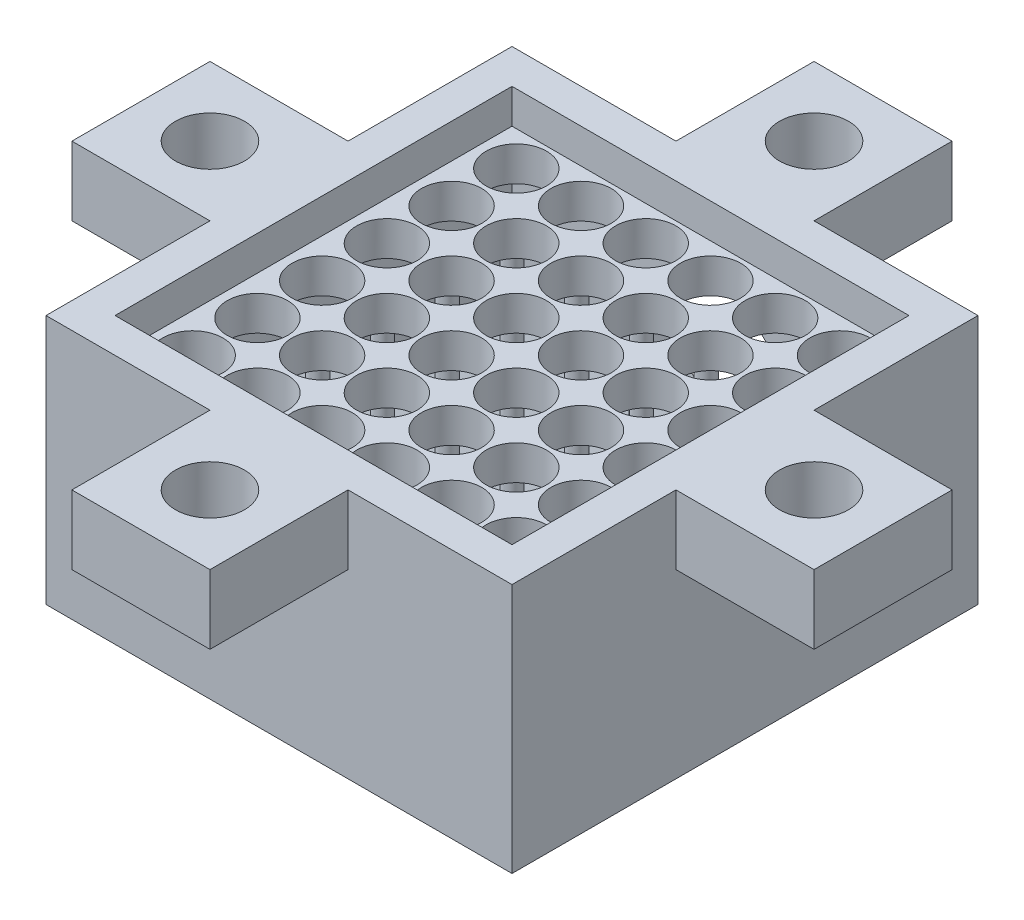
SolidWorks part; units mm, degrees
note: '?' marks a value the reader was unsure of.
ref_plane "Front Plane" through (0, 0, 0) normal (0, 0, 1) x (1, 0, 0)
ref_plane "Top Plane" through (0, 0, 0) normal (0, 1, 0) x (1, 0, 0)
ref_plane "Right Plane" through (0, 0, 0) normal (1, 0, 0) x (0, 0, -1)
sketch "Sketch1" plane through (0, 0, 0) normal (0, 1, 0) x (1, 0, 0)
  line L0 (-13.5, 13.5) -> (13.5, 13.5)
  line L1 (-11.5, -11.5) -> (11.5, -11.5)
  line L2 (-11.5, -11.5) -> (-11.5, 11.5)
  line L3 (-11.5, 11.5) -> (11.5, 11.5)
  line L4 (11.5, -11.5) -> (11.5, 11.5)
  line L5 (-11.5, -11.5) -> (11.5, 11.5) construction
  line L6 (-11.5, 11.5) -> (11.5, -11.5) construction
  line L7 (13.5, -13.5) -> (13.5, 13.5)
  line L8 (-13.5, -13.5) -> (13.5, -13.5)
  line L9 (-13.5, -13.5) -> (-13.5, 13.5)
  point P0 (0, 0)
  dimension "D1" = 23
  dimension "D2" = 2
extrude "Boss-Extrude1" add sketch "Sketch1" along normal blind 2
sketch "Sketch2" plane through (0, 0, 0) normal (0, -1, 0) x (1, 0, 0)
  line L1 (-13.5, 13.5) -> (13.5, 13.5)
  line L2 (-13.5, 13.5) -> (-13.5, -13.5)
  line L3 (-13.5, -13.5) -> (13.5, -13.5)
  line L4 (13.5, 13.5) -> (13.5, -13.5)
  line L5 (-13.5, 13.5) -> (13.5, -13.5) construction
  line L6 (-13.5, -13.5) -> (13.5, 13.5) construction
  point P0 (0, 0)
extrude "Boss-Extrude2" add sketch "Sketch2" along normal blind 2
sketch "Sketch12" plane through (-13.5, 0, 0) normal (-1, 0, 0) x (0, 0, 1)
  line L0 (-13.5, 2) -> (13.5, 2) construction
  line L1 (-4, -2) -> (4, -2)
  line L2 (-4, -2) -> (-4, 2)
  line L3 (-4, 2) -> (4, 2)
  line L4 (4, -2) -> (4, 2)
  line L5 (-4, -2) -> (4, 2) construction
  line L6 (-4, 2) -> (4, -2) construction
  point P0 (0, 0)
  dimension "D1" = 8
extrude "Boss-Extrude9" add sketch "Sketch12" along normal blind 8
ref_axis "Axis2" through (0, 0, 0) along (0, -1, 0)?
pattern_circular "CirPattern1" count 4 over 360 about axis through (0, 0, 0) along (0, 1, 0) of "Boss-Extrude9"
sketch "Sketch20" plane through (0, 2, 0) normal (0, 1, 0) x (1, 0, 0)
  line L0 (4, -13.5) -> (-4, -21.5) construction
  circle A0 centre (0, -17.5) radius 2
  dimension "D1" = 4
extrude "Cut-Extrude11" cut sketch "Sketch20" against normal up to next
pattern_circular "CirPattern2" count 4 over 360 about axis through (0, 0, 0) along (0, 1, 0) of "Cut-Extrude11"
ref_plane "Plane1" through (0, 0, 0) normal (1, 0, 0) x (0, 0, -1)
sketch "Sketch13" plane through (0, 0, 0) normal (0, 1, 0) x (1, 0, 0)
  line L0 (11.5, -11.5) -> (11.5, 11.5) construction
  line L1 (11.5, 11.5) -> (-11.5, 11.5) construction
  circle A0 centre (9.5, 9.5) radius 1.75
  dimension "D1" = 3.5
  dimension "D2" = 2
  dimension "D3" = 2
extrude "Cut-Extrude4" cut sketch "Sketch13" against normal up to next
pattern_linear "LPattern3" count 6 spacing 3.75 along (0, 0, 1) count 6 spacing 3.75 along (-1, 0, 0) of "Cut-Extrude4"
sketch "Sketch14" plane through (0, -2, 0) normal (0, -1, 0) x (1, 0, 0)
  line L0 (11.5, -11.5) -> (11.5, 11.5)
  line L1 (-13.5, -13.5) -> (13.5, -13.5)
  line L2 (-13.5, -13.5) -> (-13.5, 13.5)
  line L3 (-13.5, 13.5) -> (13.5, 13.5)
  line L4 (13.5, -13.5) -> (13.5, 13.5)
  line L5 (-13.5, -13.5) -> (13.5, 13.5) construction
  line L6 (-13.5, 13.5) -> (13.5, -13.5) construction
  line L7 (-11.5, 11.5) -> (11.5, 11.5)
  line L8 (-11.5, -11.5) -> (-11.5, 11.5)
  line L9 (-11.5, -11.5) -> (11.5, -11.5)
  point P0 (0, 0)
  dimension "D1" = 2
extrude "Boss-Extrude10" add sketch "Sketch14" along normal blind 8.5
sketch "Sketch16" plane through (11.5, 0, 0) normal (-1, 0, 0) x (0, 0, 1)
  line L0 (11.5, -10.5) -> (-11.5, -10.5)
  line L1 (-11.5, -10.5) -> (-11.5, -9.5)
  line L2 (11.5, -10.5) -> (11.5, -2) construction
  line L3 (11.5, -3) -> (11.5, -10.5)
  line L4 (-11.5, -10.5) -> (-11.5, -2) construction
  line L5 (-11.5, -9.5) -> (11.5, -3)
  dimension "D1" = 7.5
  dimension "D2" = 1
extrude "Boss-Extrude11" add sketch "Sketch16" along normal up to surface (23 mm away) up to face at (-11.5, -6.25, 0)
sketch "Sketch17" plane through (0, 0, -13.5) normal (0, 0, -1) x (-1, 0, 0)
  line L1 (-13.5, -6.25) -> (13.5, -6.25) construction
  line L2 (-13.5, 2) -> (-13.5, -10.5) construction
  line L3 (13.5, 2) -> (13.5, -10.5) construction
  circle A0 centre (0, -6.25) radius 4.25
  dimension "D1" = 8.5
  dimension "D2" = 4.25
sketch "Sketch18" plane through (0, -10.5, 0) normal (0, -1, 0) x (1, 0, 0)
  line L1 (13.5, 13.5) -> (-13.5, 13.5)
  line L2 (13.5, 13.5) -> (13.5, -13.5)
  line L3 (13.5, -13.5) -> (-13.5, -13.5)
  line L4 (-13.5, 13.5) -> (-13.5, -13.5)
  line L5 (13.5, 13.5) -> (-13.5, -13.5) construction
  line L6 (13.5, -13.5) -> (-13.5, 13.5) construction
  point P0 (0, 0)
extrude "Boss-Extrude12" add sketch "Sketch18" along normal blind 2
extrude "Cut-Extrude10" cut sketch "Sketch17" against normal up to surface (2 mm away) up to face at (0, -5.75, -11.5)
sketch "Sketch19" plane through (0, -2, 0) normal (0, -1, 0) x (1, 0, 0)
  line L0 (11.5, 11.5) -> (-11.5, -11.5) construction
  line L1 (0, 0) -> (3.75, 0) construction
  line L2 (0, 0) -> (0, 3.75) construction
  line L3 (0, 3.75) -> (-3.75, 3.75) construction
  line L4 (3.75, 0) -> (3.75, 3.75) construction
  line L5 (3.75, 3.75) -> (7.5, 3.75) construction
  line L6 (7.5, 3.75) -> (7.5, 7.5) construction
  line L7 (7.5, 7.5) -> (3.75, 7.5) construction
  line L8 (3.75, 7.5) -> (0, 7.5) construction
  line L9 (0, 7.5) -> (-3.75, 7.5) construction
  line L10 (-3.75, 7.5) -> (-7.5, 7.5) construction
  line L11 (-7.5, 7.5) -> (-7.5, 3.75) construction
  line L12 (-7.5, 3.75) -> (-7.5, 0) construction
  line L13 (-7.5, 0) -> (-3.75, 0) construction
  line L14 (-3.75, 0) -> (-3.75, -3.75) construction
  line L15 (-3.75, -3.75) -> (-7.5, -3.75) construction
  line L16 (-7.5, -3.75) -> (-7.5, -7.5) construction
  line L17 (-7.5, -7.5) -> (-3.75, -7.5) construction
  line L18 (-3.75, -7.5) -> (0, -7.5) construction
  line L19 (0, -7.5) -> (0, -3.75) construction
  line L20 (0, -3.75) -> (3.75, -3.75) construction
  line L21 (3.75, -3.75) -> (3.75, -7.5) construction
  line L22 (3.75, -7.5) -> (7.5, -7.5) construction
  line L23 (7.5, -7.5) -> (7.5, -3.75) construction
  line L24 (7.5, -3.75) -> (7.5, 0) construction
  circle A0 centre (0, 0) radius 0.5
  circle A1 centre (3.75, 0) radius 0.5
  circle A2 centre (0, 3.75) radius 0.5
  circle A3 centre (-3.75, 3.75) radius 0.5
  circle A4 centre (3.75, 3.75) radius 0.5
  circle A5 centre (7.5, 3.75) radius 0.5
  circle A6 centre (7.5, 7.5) radius 0.5
  circle A7 centre (3.75, 7.5) radius 0.5
  circle A8 centre (0, 7.5) radius 0.5
  circle A9 centre (-3.75, 7.5) radius 0.5
  circle A10 centre (-7.5, 7.5) radius 0.5
  circle A11 centre (-7.5, 3.75) radius 0.5
  circle A12 centre (-7.5, 0) radius 0.5
  circle A13 centre (-3.75, 0) radius 0.5
  circle A14 centre (-3.75, -3.75) radius 0.5
  circle A15 centre (-7.5, -3.75) radius 0.5
  circle A16 centre (-7.5, -7.5) radius 0.5
  circle A17 centre (-3.75, -7.5) radius 0.5
  circle A18 centre (0, -7.5) radius 0.5
  circle A19 centre (0, -3.75) radius 0.5
  circle A20 centre (3.75, -3.75) radius 0.5
  circle A21 centre (3.75, -7.5) radius 0.5
  circle A22 centre (7.5, -7.5) radius 0.5
  circle A23 centre (7.5, -3.75) radius 0.5
  circle A24 centre (7.5, 0) radius 0.5
  dimension "D1" = 1
  dimension "D2" = 3.75
extrude "Boss-Extrude13" add sketch "Sketch19" along normal up to surface (4.3913 mm away)
